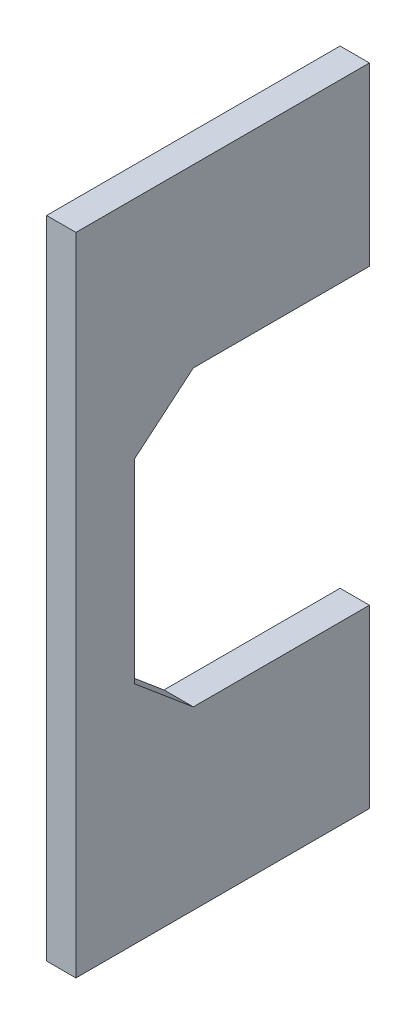
SolidWorks part; units mm, degrees
ref_plane "Front" through (0, 0, 0) normal (0, 0, 1) x (1, 0, 0)
ref_plane "Top" through (0, 0, 0) normal (0, 1, 0) x (1, 0, 0)
ref_plane "Right" through (0, 0, 0) normal (1, 0, 0) x (0, 0, -1)
sketch "Skizze1" plane through (0, 0, 0) normal (1, 0, 0) x (0, 0, -1)
  line L1 (0, 0) -> (50, 0)
  line L2 (0, 0) -> (0, 110)
  line L3 (0, 110) -> (50, 110)
  line L4 (50, 0) -> (50, 110)
  dimension "D1" = 50
  dimension "D2" = 110
extrude "Aufsatz-Linear austragen1" add sketch "Skizze1" along normal blind 5
sketch "Skizze2" plane through (5, 0, 0) normal (1, 0, 0) x (0, 0, -1)
  line L0 (50, 55) -> (10, 55) construction
  line L1 (50, 0) -> (50, 110) construction
  line L2 (10, 38.391) -> (10, 71.609)
  line L3 (10, 71.609) -> (20, 80)
  line L4 (20, 80) -> (50, 80)
  line L5 (50, 80) -> (50, 30)
  line L6 (10, 38.391) -> (20, 30)
  line L7 (20, 30) -> (50, 30)
  dimension "D1" = 30
  dimension "D2" = 50
  dimension "D3" = 140
  dimension "D4" = 40
extrude "Schnitt-Linear austragen1" cut sketch "Skizze2" against normal through all
